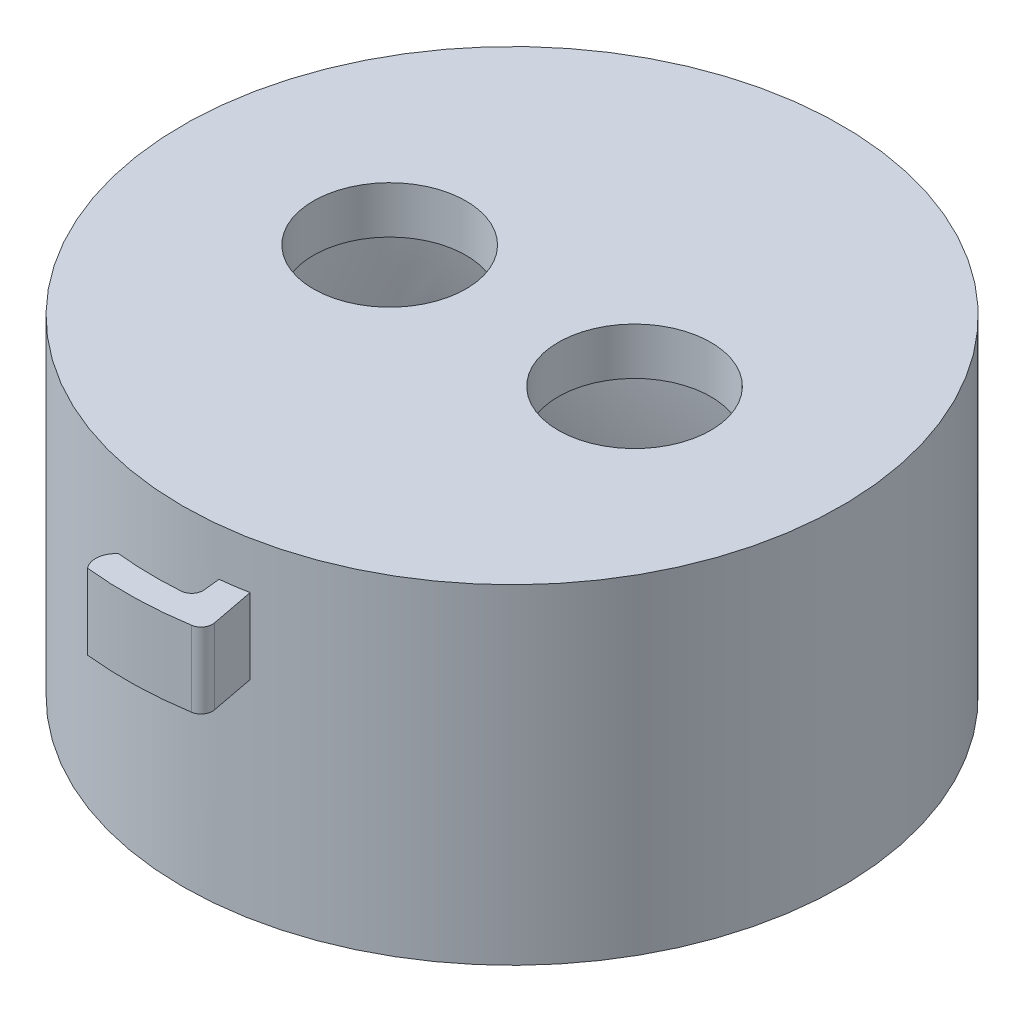
SolidWorks part; units mm, degrees
ref_plane "Plano frontal" through (0, 0, 0) normal (0, 0, 1) x (1, 0, 0)
ref_plane "Plano superior" through (0, 0, 0) normal (0, 1, 0) x (1, 0, 0)
ref_plane "Plano direito" through (0, 0, 0) normal (1, 0, 0) x (0, 0, -1)
sketch "Esboço1" plane through (0, 0, 0) normal (0, 1, 0) x (1, 0, 0)
  circle A0 centre (0, 0) radius 35
  dimension "D1" = 70
extrude "Ressalto-extrusão1" add sketch "Esboço1" along normal mid plane 35
sketch "Esboço2" plane through (0, 17.5, 0) normal (0, 1, 0) x (1, 0, 0)
  line L0 (-13, 0) -> (13, 0) construction
  circle A0 centre (-13, 0) radius 8.1
  circle A1 centre (13, 0) radius 8.1
  point P4 (0, 0)
  dimension "D2" = 16.2
  dimension "D1" = 26
extrude "Corte-extrusão1" cut sketch "Esboço2" against normal through all
sketch "Esboço4" plane through (0, -17.5, 0) normal (0, -1, 0) x (1, 0, 0)
  circle A0 centre (0, 0) radius 30.25
  dimension "D1" = 60.5
ref_plane "Plano1" through (0, 12.5, 0) normal (0, 1, 0) x (1, 0, 0)
sketch "Esboço5" plane through (0, 12.5, 0) normal (0, 1, 0) x (1, 0, 0)
  circle A0 centre (0, 0) radius 29.5
  dimension "D1" = 59
loft "Loft de corte1" cut profiles "Esboço4", "Esboço5" connector at (-27.9108, -17.5, 11.6639) connector at (-29.1483, 12.5, -4.5416)
sketch "Esboço6" plane through (0, 12.5, 0) normal (0, 1, 0) x (1, 0, 0)
  line L0 (-4, -37.7889) -> (4, -37.7889) construction
  line L1 (-4.3158, -40.7722) -> (0, 0) construction
  line L2 (-4.3158, -40.7722) -> (7.6842, -40.2735) construction
  line L3 (1.6842, -40.5228) -> (0, 0) construction
  line L4 (7.4559, -39.077) -> (6.5597, -34.3798)
  line L5 (3.8716, -36.5761) -> (3.6842, -34.8056)
  arc A0 (-4.3158, -40.7722) -> (-4, -37.7889) centre (-2.6662, -39.4384) cw
  arc A2 (2.7656, -37.8992) -> (-4, -37.7889) centre (0, 0) cw
  arc A3 (6.4664, -40.4869) -> (-4.3158, -40.7722) centre (0, 0) cw
  circle A4 centre (0, 0) radius 35 construction
  arc A5 (-3.6842, -34.8056) -> (6.5597, -34.3798) centre (0, 0) ccw
  arc A6 (6.4664, -40.4869) -> (7.4559, -39.077) centre (6.2772, -39.3019) ccw
  arc A7 (2.7656, -37.8992) -> (3.8716, -36.5761) centre (2.6783, -36.7024) ccw
  point P3 (0, -37.7889)
  dimension "D1" = 38
  dimension "D2" = 8
  dimension "D3" = 41
  dimension "D5" = 1.2
  dimension "D4" = 12
extrude "Ressalto-extrusão2" add sketch "Esboço6" against normal blind 8 contours A7 A2 A0 A3 A6 L4 A5 L5 region at (2.1841, 12.5, 38.6732)
